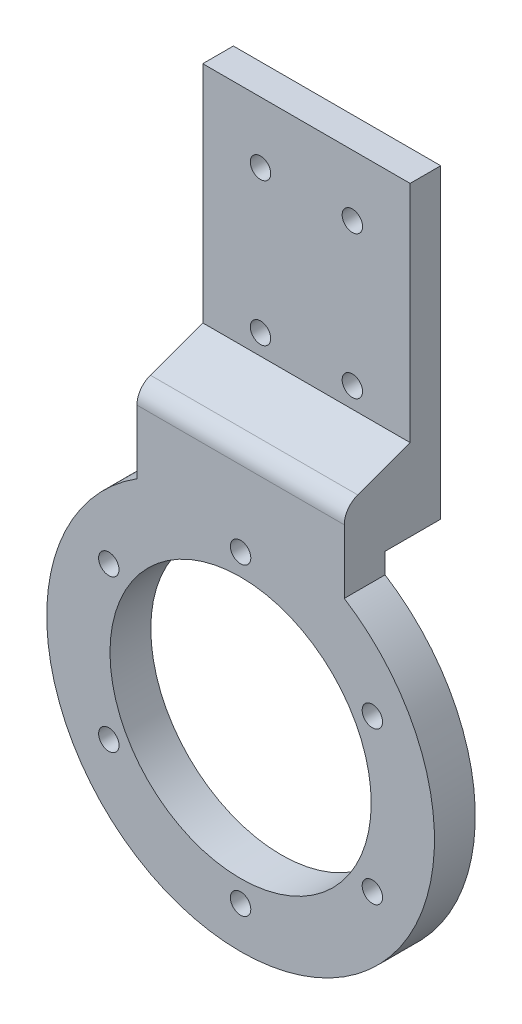
SolidWorks part; units mm, degrees
ref_plane "Front Plane" through (0, 0, 0) normal (0, 0, 1) x (1, 0, 0)
ref_plane "Top Plane" through (0, 0, 0) normal (0, 1, 0) x (1, 0, 0)
ref_plane "Right Plane" through (0, 0, 0) normal (1, 0, 0) x (0, 0, -1)
sketch "Sketch1" plane through (0, 0, 0) normal (0, 0, 1) x (1, 0, 0)
  line L0 (-25.4, 40.1384) -> (-25.4, 120.1384)
  line L1 (-25.4, 120.1384) -> (25.4, 120.1384)
  line L2 (25.4, 120.1384) -> (25.4, 40.1384)
  line L4 (-11.25, 105.1384) -> (11.25, 105.1384) construction
  line L5 (-11.25, 105.1384) -> (-11.25, 70.1384) construction
  line L6 (-11.25, 70.1384) -> (11.25, 70.1384) construction
  line L7 (11.25, 105.1384) -> (11.25, 70.1384) construction
  line L9 (-25.4, 45.1384) -> (25.4, 45.1384)
  line L10 (-25.4, 55.1384) -> (25.4, 55.1384)
  circle A2 centre (-11.25, 105.1384) radius 2.5
  circle A3 centre (11.25, 105.1384) radius 2.5
  circle A4 centre (11.25, 70.1384) radius 2.5
  circle A5 centre (-11.25, 70.1384) radius 2.5
  arc A6 (-25.4, 40.1384) -> (25.4, 40.1384) centre (0, 0) ccw
  circle A8 centre (0, 0) radius 37.28 construction
  circle A9 centre (0, 37.28) radius 2.5
  circle A10 centre (32.2854, 18.64) radius 2.5
  circle A11 centre (32.2854, -18.64) radius 2.5
  circle A12 centre (0, -37.28) radius 2.5
  circle A13 centre (-32.2854, -18.64) radius 2.5
  circle A14 centre (-32.2854, 18.64) radius 2.5
  circle A15 centre (0, 0) radius 32
  point P13 (0, 70.1384)
  point P32 (0, 0)
  point P40 (0, 120.1384)
  dimension "D1" = 95
  dimension "D4" = 5
  dimension "D8" = 74.56
  dimension "D9" = 5
  dimension "D13" = 64
  dimension "D2" = 50.8
  dimension "D3" = 5
  dimension "D5" = 35
  dimension "D6" = 15
  dimension "D7" = 22.5
  dimension "D11" = 25
  dimension "D12" = 10
  dimension "D10" = 6
extrude "5" add sketch "Sketch1" along normal blind 7.5 contours L0 L9 L2 L1 A5 A4 A3 A2 region at (0, 87.6384, 0)
extrude "Boss-Extrude1" add sketch "Sketch1<3>" along normal blind 13.63 contours L10 L0 L9 L2 region at (0, 50.1384, 0)
sketch "Sketch1<3>" plane through (0, 0, 0) normal (0, 0, 1) x (1, 0, 0) same geometry as "Sketch1"
extrude "Boss-Extrude2" add sketch "Sketch1<4>" along normal blind 10 from surface contours A6 L2 L9 L0 A14 A13 A12 A11 A10 A9 | L10 L0 L9 L2 region at (-24.0731, 42.6384, 0) region at (0, 50.1384, 0) starting at face at (0, 50.1384, 13.63)
sketch "Sketch1<4>" plane through (0, 0, 0) normal (0, 0, 1) x (1, 0, 0) same geometry as "Sketch1"
chamfer "Chamfer1" distance 10 angle 70 1 edges at (0, 55.1384, 7.5) first distance on face at (-8.75, 70.1384, 7.5)
fillet "Fillet1" radius 5 1 edges at (0, 59.2675, 23.63)
